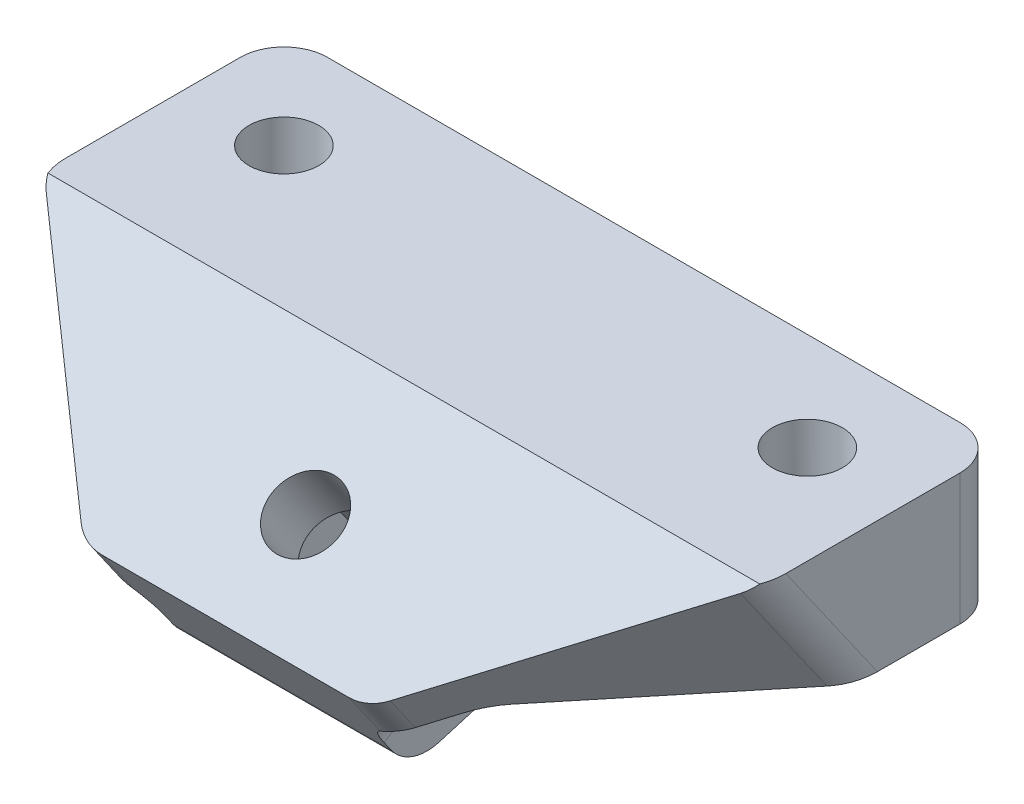
SolidWorks part; units mm, degrees
material "ABS"
ref_plane "Front" through (0, 0, 0) normal (0, 0, 1) x (1, 0, 0)
ref_plane "Top" through (0, 0, 0) normal (0, 1, 0) x (1, 0, 0)
ref_plane "Right" through (0, 0, 0) normal (1, 0, 0) x (0, 0, -1)
sketch "Esquisse1" plane through (0, 0, 0) normal (1, 0, 0) x (0, 0, -1)
  line L0 (11, 0) -> (0, 0)
  line L1 (0, 0) -> (-8.1915, -5.7358)
  dimension "D1" = 145
  dimension "D2" = 11
  dimension "D3" = 10
extrude "Extru.-Mince1" add sketch "Esquisse1" along normal mid plane 33 thin thin type one direction reverse wall 6
sketch "Esquisse7" plane through (-16.5, 0, 0) normal (-1, 0, 0) x (0, 0, 1)
  line L0 (-1.8918, -6) -> (5.082, -6)
  line L1 (5.082, -6) -> (7.0444, -7.3741)
  line L2 (4.7501, -10.6507) -> (8.1915, -5.7358) construction
  line L3 (7.0444, -7.3741) -> (4.7501, -10.6507)
  line L4 (4.7501, -10.6507) -> (-1.8918, -6)
  line L5 (0, 0) -> (8.1915, -5.7358) construction
  dimension "D1" = 2
extrude "Enlèv. mat.-Extru.5" cut sketch "Esquisse7" against normal through all
sketch "Esquisse6" plane through (0, 0, 0) normal (1, 0, 0) x (0, 0, -1)
  line L1 (1.8918, -6) -> (11, -6)
  line L2 (11, -6) -> (-4.7501, -10.6507)
  line L3 (-8.1915, -5.7358) -> (-4.7501, -10.6507)
  line L4 (-8.1915, -5.7358) -> (-5.082, -6)
  line L5 (-5.082, -6) -> (1.8918, -6)
  line L6 (-7.0444, -7.3741) -> (-8.1915, -5.7358) construction
  line L7 (11, 0) -> (11, -6) construction
extrude "Boss.-Extru.1" add sketch "Esquisse6" along normal mid plane 10
sketch "Esquisse2" plane through (0, 0, 0) normal (0, 1, 0) x (1, 0, 0)
  line L0 (0, -50) -> (0, 50) construction
  line L1 (16.5, 11) -> (-16.5, 11) construction
  line L2 (-16.5, 11) -> (-16.5, 0) construction
  circle A0 centre (-12, 6.5) radius 1.6
  circle A1 centre (12, 6.5) radius 1.6
  dimension "D1" = 24
  dimension "D2" = 4.5
  dimension "D3" = 3.2
  dimension "D4" = 4.5
extrude "Enlèv. mat.-Extru.1" cut sketch "Esquisse2" against normal through all
sketch "Esquisse3" plane through (0, 0, 0) normal (0, 0.8192, 0.5736) x (1, 0, 0)
  line L0 (16.5, -10) -> (-16.5, -10) construction
  circle A0 centre (0, -5.5) radius 1.6
  dimension "D1" = 4.5
  dimension "D2" = 3.2
extrude "Enlèv. mat.-Extru.2" cut sketch "Esquisse3" against normal through all
sketch "Esquisse4" plane through (0, 0, 0) normal (0, 1, 0) x (1, 0, 0)
  line L0 (16.5, 11) -> (-16.5, 11) construction
  line L1 (-9.25, 8.0877) -> (-12, 9.6754)
  line L2 (-12, 9.6754) -> (-14.75, 8.0877)
  line L3 (-14.75, 8.0877) -> (-14.75, 4.9123)
  line L4 (-14.75, 4.9123) -> (-12, 3.3246)
  line L5 (-12, 3.3246) -> (-9.25, 4.9123)
  line L6 (-9.25, 4.9123) -> (-9.25, 8.0877)
  line L7 (14.75, 8.0877) -> (12, 9.6754)
  line L8 (12, 9.6754) -> (9.25, 8.0877)
  line L9 (9.25, 8.0877) -> (9.25, 4.9123)
  line L10 (9.25, 4.9123) -> (12, 3.3246)
  line L11 (12, 3.3246) -> (14.75, 4.9123)
  line L12 (14.75, 4.9123) -> (14.75, 8.0877)
  circle A0 centre (-12, 6.5) radius 2.75 construction
  circle A1 centre (12, 6.5) radius 2.75 construction
  circle A2 centre (12, 6.5) radius 1.6 construction
  circle A3 centre (-12, 6.5) radius 1.6 construction
  dimension "D1" = 5.5
  dimension "D2" = 30
extrude "Enlèv. mat.-Extru.3" cut sketch "Esquisse4" against normal through all from offset 3 offset against normal yes
sketch "Esquisse5" plane through (0, 0, 0) normal (0, 0.8192, 0.5736) x (1, 0, 0)
  line L1 (2.75, -3.9123) -> (0, -2.3246)
  line L2 (0, -2.3246) -> (-2.75, -3.9123)
  line L3 (-2.75, -3.9123) -> (-2.75, -7.0877)
  line L4 (-2.75, -7.0877) -> (0, -8.6754)
  line L5 (0, -8.6754) -> (2.75, -7.0877)
  line L6 (2.75, -7.0877) -> (2.75, -3.9123)
  circle A0 centre (0, -5.5) radius 2.75 construction
  circle A1 centre (0, -5.5) radius 1.6 construction
  dimension "D1" = 5.5
extrude "Enlèv. mat.-Extru.4" cut sketch "Esquisse5" against normal through all from offset 3 offset against normal yes
chamfer "Chanfrein1" distance 10 angle 45 2 edges at (-16.5, -6.5549, 7.6179) (16.5, -6.5549, 7.6179)
fillet "Congé1" radius 2 15 edges at (-16.5, -3, -2.1006) (5.75, -7.3741, 7.0444) (6.5, -6.5549, 7.6179) (-6.5, -6.5549, 7.6179) (16.5, -3, -2.1006) (6.9478, -6, 5.082) (16.5, -3, -11) (-6.9478, -6, 5.082) (-5.75, -7.3741, 7.0444) (-5, -6.687, 6.0632) (5, -6.687, 6.0632) (5, -6, -2.959) (0, -10.6507, 4.7501) (-5, -6, -2.959) (-16.5, -3, -11)
